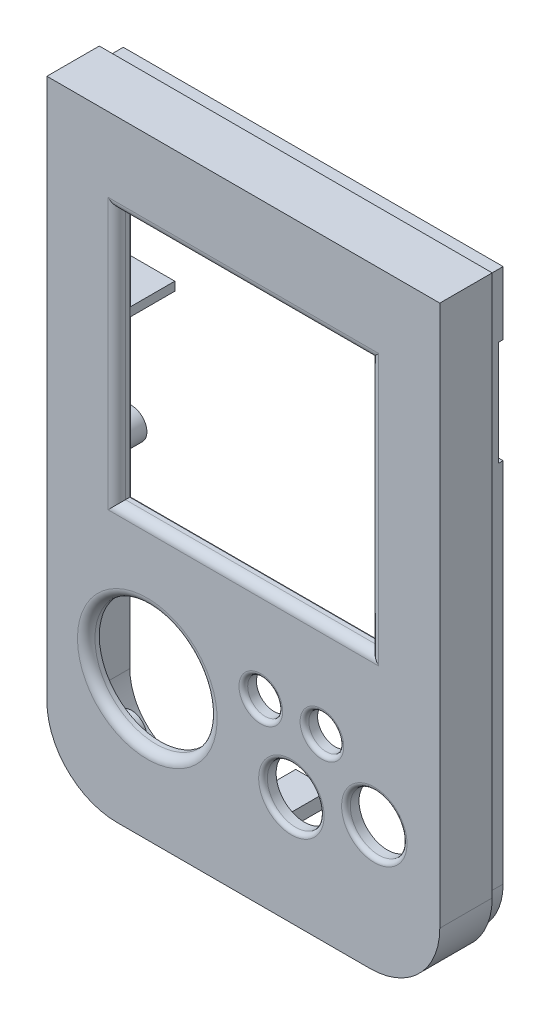
SolidWorks part; units mm, degrees
ref_plane "前视基准面" through (0, 0, 0) normal (0, 0, 1) x (1, 0, 0)
ref_plane "上视基准面" through (0, 0, 0) normal (0, 1, 0) x (1, 0, 0)
ref_plane "右视基准面" through (0, 0, 0) normal (1, 0, 0) x (0, 0, -1)
sketch "草图1" plane through (0, 0, 0) normal (0, 0, 1) x (1, 0, 0)
  line L1 (-45, 70) -> (0, 70)
  line L2 (-45, 70) -> (-45, 8)
  line L3 (-37, 0) -> (-8, 0)
  line L4 (0, 70) -> (0, 8)
  arc A2 (-37, 0) -> (-45, 8) centre (-37, 8) cw
  arc A3 (-8, 0) -> (0, 8) centre (-8, 8) ccw
  point P7 (0, 70)
  point P9 (-45, 0)
  point P10 (-45, 70)
  point P13 (0, 0)
  dimension "D3" = 8
  dimension "D1" = 45
  dimension "D2" = 70
extrude "凸台-拉伸1" add sketch "草图1" along normal blind 8 contours L1 L4 A3 L3 A2 L2
shell "抽壳2" thickness 1.5 removed face at (-22.5, 25.4477, 0)
sketch "草图4" plane through (0, 0, 0) normal (0, 0, -1) x (-1, 0, 0)
  line L0 (22.5, 68.5) -> (22.5, 50068.5) construction
  line L1 (8, 60.5) -> (37, 60.5)
  line L2 (8, 60.5) -> (8, 31.5)
  line L3 (8, 31.5) -> (37, 31.5)
  line L4 (37, 60.5) -> (37, 31.5)
  line L5 (43.5, 68.5) -> (1.5, 68.5) construction
  line L6 (45, 70) -> (0, 70) construction
  line L7 (45, 70) -> (45, 8) construction
  line L8 (0, 70) -> (0, 8) construction
  circle A0 centre (33.5, 16) radius 7
  circle A1 centre (7.5, 14.5) radius 3.25
  circle A2 centre (17, 12.5) radius 3.25
  circle A3 centre (13.5, 20.5) radius 2
  circle A4 centre (20.5, 20.5) radius 2
  point P8 (22.5, 68.5)
  dimension "D4" = 14
  dimension "D7" = 6.5
  dimension "D8" = 6.5
  dimension "D13" = 4
  dimension "D14" = 4
  dimension "D1" = 29
  dimension "D2" = 29
  dimension "D3" = 9.5
  dimension "D5" = 11.5
  dimension "D6" = 54
  dimension "D9" = 7.5
  dimension "D10" = 17
  dimension "D11" = 2
  dimension "D12" = 3.5
  dimension "D15" = 8
  dimension "D16" = 7
  dimension "D17" = 13.5
extrude "切除-拉伸3" cut sketch "草图4" against normal through all
fillet "圆角1" radius 1 4 edges at (-22.5, 60.5, 8) (-8, 46, 8) (-22.5, 31.5, 8) (-37, 46, 8)
fillet "圆角2" radius 1 1 edges at (-40.5, 16, 8)
fillet "圆角3" radius 0.5 4 edges at (-15.5, 20.5, 8) (-22.5, 20.5, 8) (-10.75, 14.5, 8) (-20.25, 12.5, 8)
sketch "草图5" plane through (0, 0, 6.5) normal (0, 0, -1) x (-1, 0, 0)
  line L1 (6.65, 65.75) -> (38.35, 65.75)
  line L2 (6.65, 65.75) -> (6.65, 30.15)
  line L3 (6.65, 30.15) -> (38.35, 30.15)
  line L4 (38.35, 65.75) -> (38.35, 30.15)
  line L6 (22.5, 55.8413) -> (22.5, 50055.8413) construction
  line L7 (8, 31.5) -> (8, 60.5) construction
  line L8 (37, 60.5) -> (37, 31.5) construction
  line L9 (37, 31.5) -> (8, 31.5) construction
  line L10 (39.35, 66.75) -> (39.35, 29.15)
  line L11 (5.65, 29.15) -> (39.35, 29.15)
  line L12 (5.65, 66.75) -> (5.65, 29.15)
  line L13 (5.65, 66.75) -> (39.35, 66.75)
  dimension "D1" = 31.7
  dimension "D2" = 35.6
  dimension "D3" = 1.35
  dimension "D4" = 1
extrude "凸台-拉伸2" add sketch "草图5" along normal blind 1.4
sketch "草图6" plane through (0, 0, 6.5) normal (0, 0, -1) x (-1, 0, 0)
  line L0 (45, 70) -> (0, 70) construction
  line L1 (0, 70) -> (0, 8) construction
  line L2 (4.5, 65.5) -> (4.5, 35.25) construction
  line L3 (22.5, -955.0295) -> (22.5, 49044.9705) construction
  line L4 (45, 70) -> (45, 8) construction
  circle A0 centre (4.5, 65.5) radius 1.75
  circle A1 centre (4.5, 65.5) radius 0.75
  circle A2 centre (4.5, 35.25) radius 1.75
  circle A3 centre (4.5, 35.25) radius 0.75
  circle A4 centre (4.5, 5) radius 1.75
  circle A5 centre (4.5, 5) radius 0.75
  circle A6 centre (40.5, 5) radius 0.75
  circle A7 centre (40.5, 5) radius 1.75
  circle A8 centre (40.5, 35.25) radius 0.75
  circle A9 centre (40.5, 35.25) radius 1.75
  circle A10 centre (40.5, 65.5) radius 0.75
  circle A11 centre (40.5, 65.5) radius 1.75
  dimension "D1" = 3.5
  dimension "D4" = 1
  dimension "D2" = 4.5
  dimension "D3" = 4.5
  dimension "D6" = 30.25
  dimension "D5" = 3
extrude "凸台-拉伸3" add sketch "草图6" along normal blind 3.7
sketch "草图7" plane through (0, 0, 0) normal (0, 0, -1) x (-1, 0, 0)
  line L0 (45, 70) -> (45, 8) construction
  line L1 (0, 70) -> (45, 70)
  line L2 (0, 70) -> (0, 8)
  line L3 (8, 0) -> (37, 0)
  line L4 (45, 70) -> (45, 8)
  line L5 (37, 0) -> (8, 0) construction
  line L6 (0.75, 69.25) -> (44.25, 69.25)
  line L7 (44.25, 69.25) -> (44.25, 8)
  line L8 (8, 0.75) -> (37, 0.75)
  line L9 (0.75, 69.25) -> (0.75, 8)
  arc A0 (37, 0) -> (45, 8) centre (37, 8) ccw
  arc A1 (0, 8) -> (8, 0) centre (8, 8) ccw
  arc A2 (37, 0.75) -> (44.25, 8) centre (37, 8) ccw
  arc A3 (0.75, 8) -> (8, 0.75) centre (8, 8) ccw
  dimension "D1" = 8
  dimension "D2" = 0.75
extrude "切除-拉伸4" cut sketch "草图7" against normal blind 2
sketch "草图8" plane through (0, 0, 0) normal (0, 0, -1) x (-1, 0, 0)
  line L0 (0.75, 69.25) -> (0.75, 8) construction
  line L1 (0.75, 62) -> (1.5, 62)
  line L2 (0.75, 62) -> (0.75, 50)
  line L3 (0.75, 50) -> (1.5, 50)
  line L4 (1.5, 62) -> (1.5, 50)
  line L5 (1.5, 68.5) -> (1.5, 8) construction
  line L6 (45, 70) -> (0, 70) construction
  dimension "D1" = 8
  dimension "D2" = 12
extrude "切除-拉伸5" cut sketch "草图8" against normal blind 0.5
sketch "草图9" plane through (0, 0, 6.5) normal (0, 0, -1) x (-1, 0, 0)
  line L0 (43.5, 68.5) -> (43.5, 8) construction
  line L1 (43.5, 49) -> (38.35, 49)
  line L2 (43.5, 49) -> (43.5, 48)
  line L3 (43.5, 48) -> (38.35, 48)
  line L4 (38.35, 49) -> (38.35, 48)
  line L5 (38.35, 30.15) -> (38.35, 65.75) construction
  line L6 (45, 70) -> (0, 70) construction
  line L7 (37, 1.5) -> (8, 1.5) construction
  line L8 (20.5, 7.5) -> (24.5, 7.5)
  line L9 (20.5, 7.5) -> (20.5, 6)
  line L10 (20.5, 6) -> (24.5, 6)
  line L11 (24.5, 7.5) -> (24.5, 6)
  line L12 (22.5, -944.5131) -> (22.5, 49055.4869) construction
  line L13 (0, 70) -> (0, 8) construction
  line L14 (45, 70) -> (45, 8) construction
  dimension "D1" = 21
  dimension "D2" = 1
  dimension "D3" = 4
  dimension "D4" = 1.5
  dimension "D5" = 4.5
extrude "凸台-拉伸4" add sketch "草图9" along normal blind 6.5
